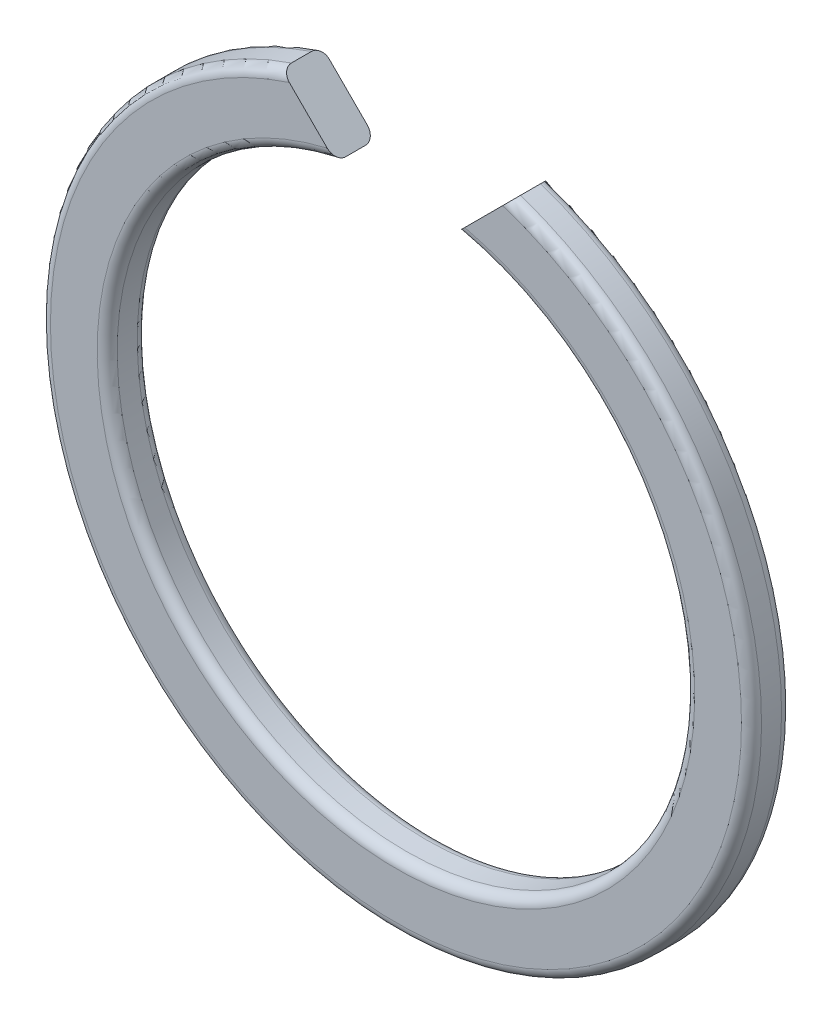
SolidWorks part; units mm, degrees
ref_plane "Front Plane" through (0, 0, 0) normal (0, 0, 1) x (1, 0, 0)
ref_plane "Top Plane" through (0, 0, 0) normal (0, 1, 0) x (1, 0, 0)
ref_plane "Right Plane" through (0, 0, 0) normal (1, 0, 0) x (0, 0, -1)
sketch "BodySke" plane through (0, 0, 0) normal (0, 0, 1) x (1, 0, 0)
  circle A0 centre (0, 0) radius 10.65
  circle A1 centre (0, 0) radius 8.65
  dimension "Groove_Width" = 2
extrude "BaseBody" add sketch "BodySke" along normal blind 1.2
sketch "SlitSke" plane through (0, 0, 0) normal (0, 0, 1) x (1, 0, 0)
  line L0 (0, 0) -> (0, 17.3673) construction
  line L1 (0, 6.65) -> (4, 10.65)
  line L2 (4, 10.65) -> (-4, 10.65)
  line L3 (0, 6.65) -> (-4, 10.65)
  circle A0 centre (0, 0) radius 10.65 construction
  point P9 (0, 9.3328)
  dimension "D2" = 6.65
  dimension "D1" = 90
extrude "Slit" cut sketch "SlitSke" along normal through all
fillet "Fillet1" radius 0.3 4 edges at (0, -8.65, 0) (0, -10.65, 0) (0, -10.65, 1.2) (0, -8.65, 1.2)
equation "\"D2@SlitSke\" = \"Groove_Diameter@BodySke\" / 2  -  \"Groove_Width@BodySke\" * 2"
